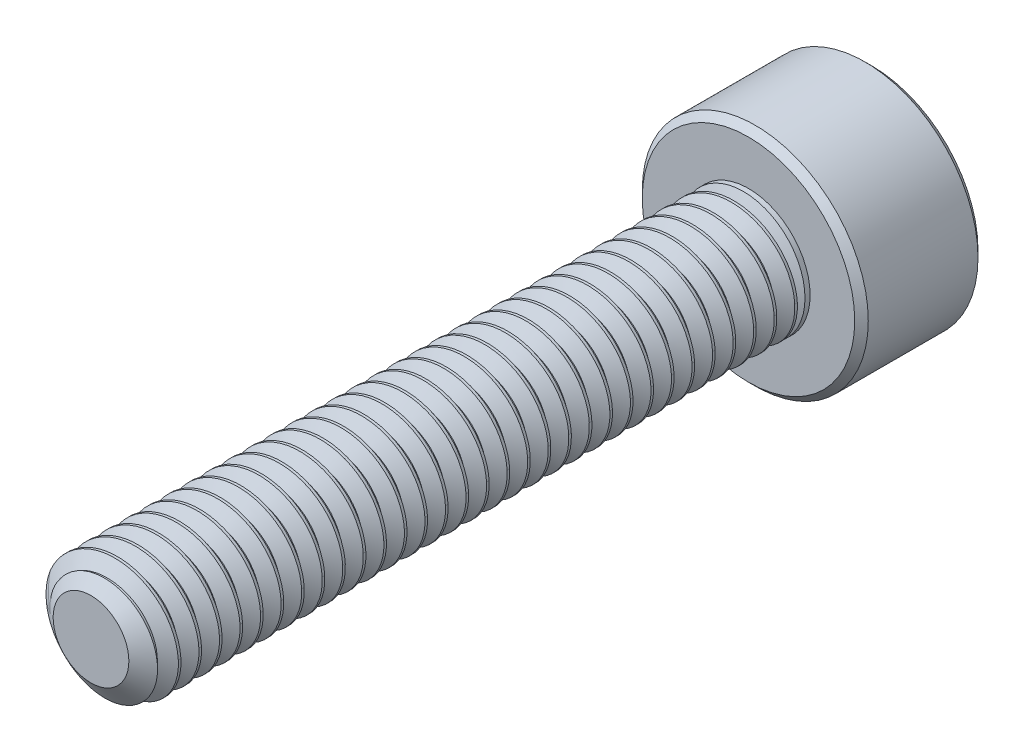
SolidWorks part; units mm, degrees
ref_plane "Front Plane" through (0, 0, 0) normal (0, 0, 1) x (1, 0, 0)
ref_plane "Top Plane" through (0, 0, 0) normal (0, 1, 0) x (1, 0, 0)
ref_plane "Right Plane" through (0, 0, 0) normal (1, 0, 0) x (0, 0, -1)
sketch "Sketch1" plane through (0, 0, 0) normal (0, 0, 1) x (1, 0, 0)
  circle A0 centre (0, 0) radius 1.5
  dimension "OD" = 3
extrude "Extrude1" add sketch "Sketch1" against normal blind 16
sketch "Sketch2" plane through (0, 0, 0) normal (0, 0, 1) x (1, 0, 0)
  circle A0 centre (0, 0) radius 1.5 construction
  circle A1 centre (0, 0) radius 1.5
curve "Helix/Spiral1" pitch 0.5 height 16.5 radius 1.5 centre (0, 0, 0) axis (0, 0, -1) start towards (0, 1, 0) parameters "pitch"=0.5
sketch "Sketch3" plane through (0, 0, 0) normal (1, 0, 0) x (0, 0, -1)
  line L0 (-0.4375, 1.5) -> (-0.25, 1.1752)
  line L1 (-0.25, 1.1752) -> (-0.1875, 1.1752)
  line L2 (-0.1875, 1.1752) -> (0, 1.5)
  line L3 (-0.4375, 1.5) -> (0, 1.5)
  line L4 (-0.2187, 1.5) -> (-0.2187, 1.1752) construction
  line L5 (-0.3437, 1.3376) -> (-0.0937, 1.3376) construction
  line L6 (0, 1.5) -> (0, -1.5) construction
  line L7 (0, -1.5) -> (16, -1.5) construction
  point P11 (2.25, -1.5)
  dimension "D1" = 0.0625
  dimension "D2" = 0.25
  dimension "D3" = 60
  dimension "D4" = 2.25
sweep "Cut-Sweep1" cut profiles "Sketch3" path "Helix/Spiral1"
sketch "Sketch4" plane through (0, 0, 0) normal (1, 0, 0) x (0, 0, -1)
  line L0 (0.4053, 1.5) -> (0, 0.9212)
  line L1 (0, 0.9212) -> (0, 1.5)
  line L2 (0.4053, 1.5) -> (0, 1.5)
  line L3 (-0.4375, 1.5) -> (0, 1.5) construction
  line L4 (0, 0) -> (7.0209, 0) construction
  dimension "D1" = 55
  dimension "D2" = 0.254
revolve "Cut-Revolve1" cut sketch "Sketch4" angle 360 about L4
sketch "Sketch5" plane through (0, 0, 0) normal (1, 0, 0) x (0, 0, -1)
  line L0 (16, -1.1822) -> (16, 1.0703) construction
  line L1 (16, 1.5) -> (0.1203, 1.5)
  line L2 (16, 1.5) -> (16, 0)
  line L3 (16, 0) -> (0.0001, 0)
  line L4 (0.0001, 1.1698) -> (0.0001, 0)
  line L5 (0.1203, 1.5) -> (0.0001, 1.1698)
  line L6 (0, 0) -> (9.9695, 0) construction
  point P3 (0.0001, 1.5)
  point P10 (0.0001, 1.5)
  dimension "D1" = 0.3302
  dimension "Thread min" = 0.0001
  dimension "D3" = 20
revolve "partially thread" [suppressed] add sketch "Sketch5" angle 360 about L6
sketch "Sketch6" plane through (0, 0, -16) normal (0, 0, -1) x (-1, 0, 0)
  circle A0 centre (0, 0) radius 2.75
  dimension "head dia" = 5.5
extrude "Extrude2" add sketch "Sketch6" along normal blind 3
sketch "Sketch7" plane through (0, 0, -19) normal (0, 0, -1) x (-1, 0, 0)
  line L1 (0, 1.4434) -> (-1.25, 0.7217)
  line L2 (-1.25, 0.7217) -> (-1.25, -0.7217)
  line L3 (-1.25, -0.7217) -> (0, -1.4434)
  line L4 (0, -1.4434) -> (1.25, -0.7217)
  line L5 (1.25, -0.7217) -> (1.25, 0.7217)
  line L6 (1.25, 0.7217) -> (0, 1.4434)
  circle A0 centre (0, 0) radius 1.25 construction
  dimension "hex dia" = 2.5
extrude "Cut-Extrude1" cut sketch "Sketch7" against normal blind 1.875
sketch "Sketch8" plane through (0, 0, -19) normal (0, 0, -1) x (-1, 0, 0)
  circle A0 centre (0, 0) radius 1.4434
extrude "Cut-Extrude2" cut sketch "Sketch8" against normal through all draft 45
chamfer "Chamfer1" distance 0.165 angle 45 2 edges at (-2.75, 0, -19) (-2.75, 0, -16)
sketch "Sketch9" plane through (0, 0, 0) normal (1, 0, 0) x (0, 0, -1)
  line L0 (0, 1.5) -> (0, -1.5) construction
  line L1 (2.75, 1.5) -> (2.75, -1.5) construction
  dimension "D1" = 2.75
sketch "Sketch10" plane through (0, 0, 0) normal (1, 0, 0) x (0, 0, -1)
  line L0 (16, 1.5) -> (16, 0)
  line L1 (16, 1.5) -> (15.875, 1.5)
  line L2 (15.875, 1.5) -> (15.2537, 0)
  line L3 (16, 0) -> (15.2537, 0)
  line L4 (16, 2.585) -> (16, -2.585) construction
  dimension "D1" = 22.5
  dimension "D2" = 0.125
revolve "Revolve1" add sketch "Sketch10" angle 360 about L3
equation "\"D3@Helix/Spiral1\" = \"screw length@Extrude1\"+\"pitch@Helix/Spiral1\""
equation "\"D1@Sketch3\" = \"pitch@Helix/Spiral1\"*.125"
equation "\"D2@Sketch3\" = \"pitch@Helix/Spiral1\"*.5"
equation "\"D1@Cut-Extrude1\" = \"hex dia@Sketch7\"*.75"
equation "\"D1@Chamfer1\" = \"head dia@Sketch6\"*.03"
equation "\"D1@Sketch9\" = \"pitch@Helix/Spiral1\"*5.5"
equation "\"D2@Sketch10\" = \"pitch@Helix/Spiral1\"*.25"
equation "\"D4@Sketch3\" = \"pitch@Helix/Spiral1\"*4.50"
